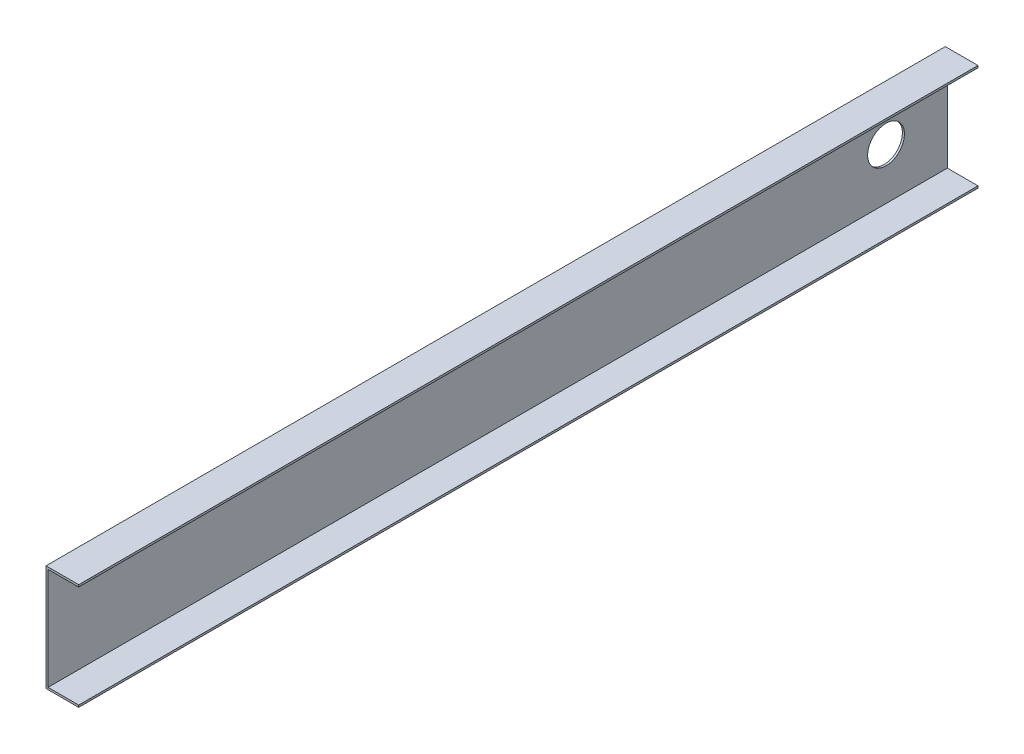
SolidWorks part; units mm, degrees
ref_plane "Plano frontal" through (0, 0, 0) normal (0, 0, 1) x (1, 0, 0)
ref_plane "Plano superior" through (0, 0, 0) normal (0, 1, 0) x (1, 0, 0)
ref_plane "Plano direito" through (0, 0, 0) normal (1, 0, 0) x (0, 0, -1)
sketch "Esboço1" plane through (0, 0, 0) normal (0, 0, 1) x (1, 0, 0)
  line L0 (8, 13) -> (0, 13)
  line L1 (0, 13) -> (0, -13)
  line L2 (0, -13) -> (8, -13)
  line L3 (8, 12.5) -> (0.5, 12.5)
  line L4 (0.5, 12.5) -> (0.5, -12.5)
  line L5 (0.5, -12.5) -> (8, -12.5)
  line L6 (8, 13) -> (8, 12.5)
  line L7 (8, -13) -> (8, -12.5)
  point P5 (0, -13)
  point P6 (0, 0)
  dimension "D1" = 26
  dimension "D2" = 8
  dimension "D3" = 0.5
extrude "Ressalto-extrusão1" add sketch "Esboço1" along normal blind 220
sketch "Esboço2" plane through (0, 0, 0) normal (-1, 0, 0) x (0, 0, 1)
  circle A0 centre (15, 0) radius 4.5
  dimension "D1" = 15
  dimension "D2" = 9
extrude "Corte-extrusão1" cut sketch "Esboço2" against normal blind 10
